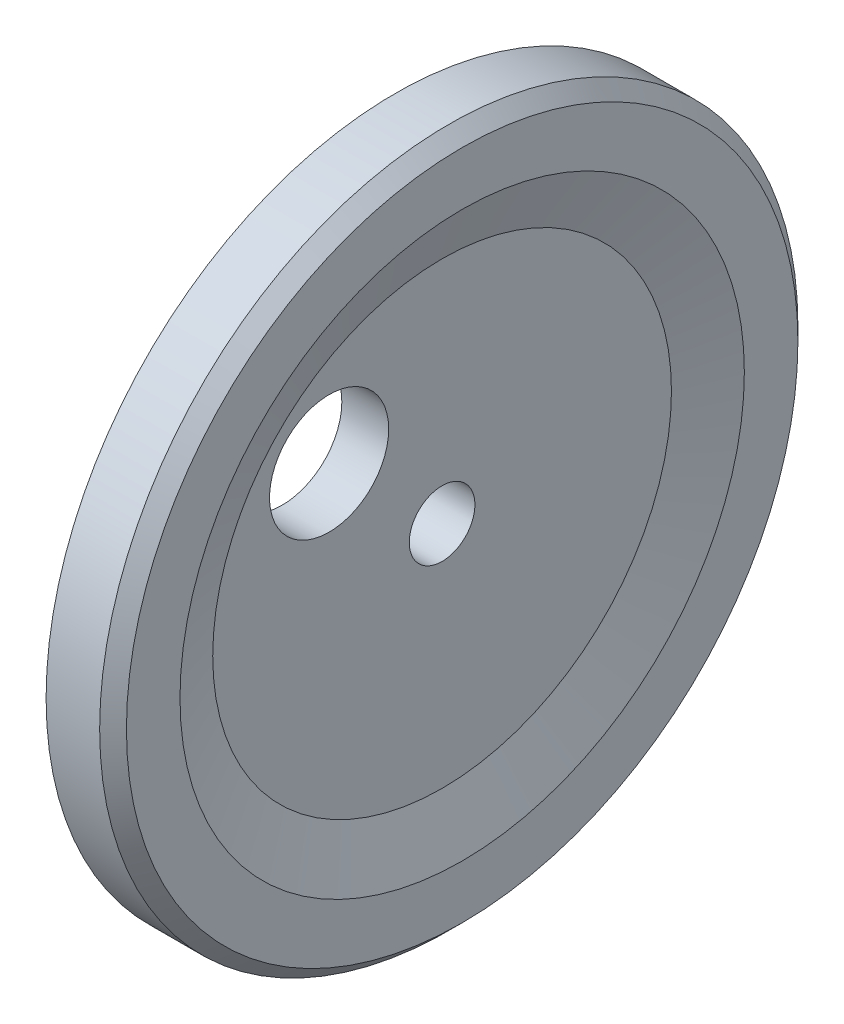
SolidWorks part; units mm, degrees
ref_plane "Front Plane" through (0, 0, 0) normal (0, 0, 1) x (1, 0, 0)
ref_plane "Top Plane" through (0, 0, 0) normal (0, 1, 0) x (1, 0, 0)
ref_plane "Right Plane" through (0, 0, 0) normal (1, 0, 0) x (0, 0, -1)
sketch "Sketch1" plane through (0, 0, 0) normal (0, 1, 0) x (1, 0, 0)
  line L1 (0, -28.6825) -> (0, 28.6825) construction
  line L2 (0, 4.9022) -> (0, 52.15)
  line L3 (0, 52.15) -> (10, 52.15)
  line L4 (10, 52.15) -> (10, 42.15)
  line L8 (7, 4.9022) -> (7, 34.26)
  line L9 (7, 34.26) -> (10, 42.15)
  line L10 (0, 4.9022) -> (7, 4.9022)
  dimension "D2" = 47.2478
  dimension "D3" = 10
  dimension "D4" = 10
  dimension "D6" = 29.3578
sketch "Sketch2" plane through (0, 0, 0) normal (0, 1, 0) x (1, 0, 0)
  line L0 (0, 0) -> (9.8109, 0)
  line L1 (-5.5, 0) -> (5.5, 0) construction
revolve "Revolve1" add sketch "Sketch1" angle 360 about L0
chamfer "Chamfer1" distance 2 angle 45 1 edges at (10, 0, 52.15)
sketch "Sketch3" plane through (7, 0, 0) normal (1, 0, 0) x (0, 0, -1)
  circle A0 centre (-16.8752, 16.2253) radius 8.9
extrude "Cut-Extrude1" cut sketch "Sketch3" against normal blind 10
